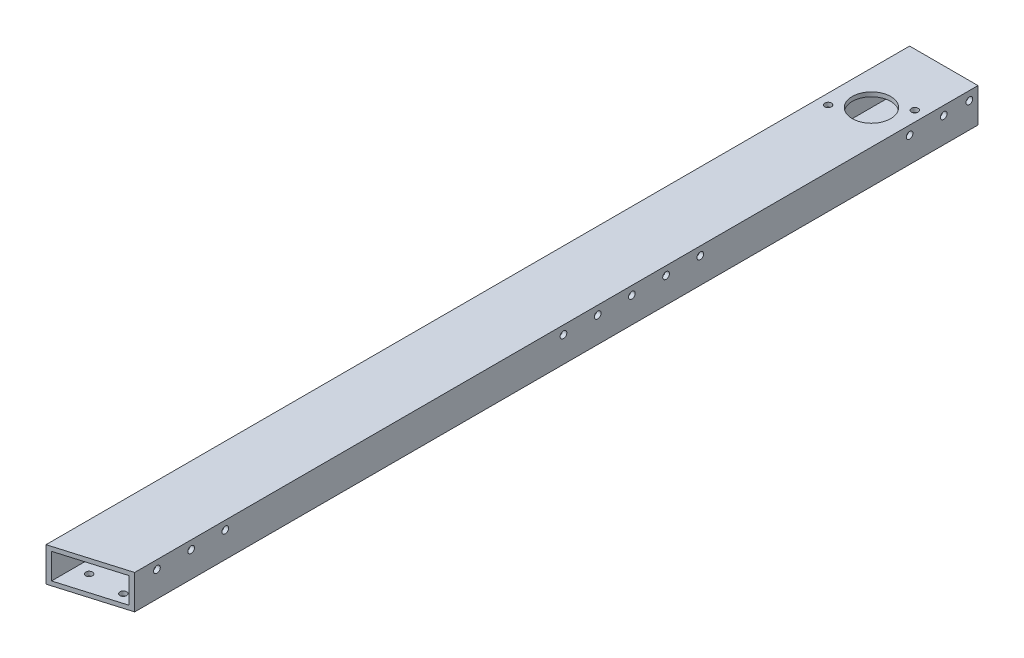
SolidWorks part; units mm, degrees
ref_plane "Front Plane" through (0, 0, 0) normal (0, 0, 1) x (1, 0, 0)
ref_plane "Top Plane" through (0, 0, 0) normal (0, 1, 0) x (1, 0, 0)
ref_plane "Right Plane" through (0, 0, 0) normal (1, 0, 0) x (0, 0, -1)
sketch "Sketch1" plane through (0, 0, 0) normal (0, 0, 1) x (1, 0, 0)
  line L0 (-22.225, 9.525) -> (22.225, 9.525)
  line L2 (-25.4, 12.7) -> (25.4, 12.7)
  line L3 (-25.4, 12.7) -> (-25.4, -12.7)
  line L4 (-25.4, -12.7) -> (25.4, -12.7)
  line L5 (25.4, 12.7) -> (25.4, -12.7)
  line L10 (22.225, 9.525) -> (22.225, -9.525)
  line L11 (-22.225, -9.525) -> (22.225, -9.525)
  line L12 (-22.225, 9.525) -> (-22.225, -9.525)
  point P12 (0, 12.7)
  point P14 (25.4, 0)
  dimension "Wall Thickness" = 3.175
  dimension "Outside Width" = 50.8
  dimension "Outside Height" = 25.4
  dimension "Inside Height" = 19.05
  dimension "Inside Width" = 44.45
sketch "Sketch2" plane through (0, 0, 0) normal (1, 0, 0) x (0, 0, -1)
  line L0 (320.675, 0) -> (-320.675, 0)
  point P4 (0, 0)
  point P7 (-320.675, 0)
  point P10 (320.675, 0)
  dimension "Length" = 641.35
sketch "Sketch3" plane through (0, 0, 0) normal (0, 0, 1) x (1, 0, 0)
  line L21 (25.4, 12.7) -> (-25.4, 12.7)
  line L22 (25.4, -12.7) -> (25.4, 12.7)
  line L23 (-25.4, -12.7) -> (25.4, -12.7)
  line L24 (-25.4, 12.7) -> (-25.4, -12.7)
  line L25 (25.4, 12.7) -> (-25.4, 12.7)
  line L26 (25.4, -12.7) -> (25.4, 12.7)
  line L27 (-25.4, -12.7) -> (25.4, -12.7)
  line L28 (-25.4, 12.7) -> (-25.4, -12.7)
  line L29 (22.225, 9.525) -> (-22.225, 9.525)
  line L30 (22.225, -9.525) -> (22.225, 9.525)
  line L31 (-22.225, -9.525) -> (22.225, -9.525)
  line L32 (-22.225, 9.525) -> (-22.225, -9.525)
  line L33 (22.225, 9.525) -> (-22.225, 9.525)
  line L34 (22.225, -9.525) -> (22.225, 9.525)
  line L35 (-22.225, -9.525) -> (22.225, -9.525)
  line L36 (-22.225, 9.525) -> (-22.225, -9.525)
  dimension "D1" = 0
  dimension "D2" = 0
extrude "Boss-Extrude1" add sketch "Sketch3" along normal up to vertex (320.675 mm away) and the other way up to vertex (320.675 mm away) up to point (0, 0, 320.675) other way up to point (0, 0, -320.675)
sketch "Drawing Reference" plane through (0, 0, 0) normal (1, 0, 0) x (0, 0, -1)
  line L0 (-320.675, 0) -> (320.675, 0) construction
  line L1 (0, -12.7) -> (0, 12.7) construction
  line L2 (-320.675, -12.7) -> (320.675, -12.7) construction
  line L5 (-320.675, 12.7) -> (320.675, 12.7) construction
  point P7 (-284.099, 0)
  point P8 (284.099, 0)
  dimension "D1" = 36.576
sketch "Sketch4" plane through (0, 12.7, 0) normal (0, 1, 0) x (1, 0, 0)
  line L0 (-25.4, -320.675) -> (25.4, -305.6274)
  line L1 (25.4, -320.675) -> (25.4, 320.675) construction
  line L2 (25.4, -320.675) -> (-25.4, -320.675)
  dimension "D1" = 16.5
extrude "Cut-Extrude1" cut sketch "Sketch4" against normal through all and the other way through all flip side to cut
sketch "Sketch8" plane through (0, 12.7, 0) normal (0, 1, 0) x (1, 0, 0)
  line L0 (0, 320.675) -> (0, 266.954) construction
  line L1 (25.4, 320.675) -> (-25.4, 320.675) construction
  circle A0 centre (0, 266.954) radius 14.2875
  dimension "D1" = 53.721
extrude "Cut-Extrude2" cut sketch "Sketch8" against normal through all
sketch "Sketch9" plane through (0, -12.7, 0) normal (0, -1, 0) x (1, 0, 0)
  line L0 (-12.7762, 284.753) -> (-12.7762, 301.263) construction
  line L1 (-12.7762, 301.263) -> (12.6238, 301.263) construction
  line L2 (12.6238, 301.263) -> (12.6238, 284.753) construction
  line L3 (12.6238, 284.753) -> (-12.7762, 284.753) construction
hole_wizard "#10 Clearance Hole1" positions "Sketch10" profile "Sketch11" hole size "#10" standard "ANSI Inch"
sketch "Sketch10" plane through (0, -12.7, 0) normal (0, -1, 0) x (-1, 0, 0)
  point P0 (-12.6238, -284.753)
  point P3 (12.7762, -284.753)
  point P6 (12.7762, -301.263)
  point P9 (-12.6238, -301.263)
sketch "Sketch11" plane through (12.6238, -12.7, 284.753) normal (1, 0, 0) x (0, 0, -1)
  line L0 (0, 0) -> (0, 6.5757)
  line L1 (0, 6.5757) -> (2.4892, 5.08)
  line L2 (2.4892, 5.08) -> (2.4892, 0)
  line L5 (2.4892, 0) -> (0, 0)
  line L10 (0, 6.5757) -> (-2.4892, 5.08) construction
  line L11 (0, -6.35) -> (0, 107.95) construction
  dimension "Hole Dia." = 4.9784
  dimension "Hole Depth" = 5.08
  dimension "Drill Angle" = 118
sketch "Sketch12" plane through (25.4, 0, 0) normal (1, 0, 0) x (0, 0, -1)
  line L0 (320.675, 533.4) -> (-305.6274, 533.4) construction
  line L1 (320.675, 520.7) -> (320.675, 546.1) construction
  line L2 (-305.6274, 546.1) -> (-305.6274, 520.7) construction
hole_wizard "#10 Clearance Hole2" positions "Sketch13" profile "Sketch14" hole size "#10" standard "ANSI Inch"
sketch "Sketch13" plane through (25.4, 0, 0) normal (1, 0, 0) x (0, 0, -1)
  point P0 (314.2868, 6.1483)
  point P3 (295.2368, 6.1483)
  point P6 (269.875, 6.1483)
sketch "Sketch14" plane through (25.4, 6.1483, -314.2868) normal (0, 1, 0) x (0, 0, -1)
  line L0 (0, 0) -> (0, 4.7977)
  line L1 (0, 4.7977) -> (2.4892, 3.302)
  line L2 (2.4892, 3.302) -> (2.4892, 0)
  line L5 (2.4892, 0) -> (0, 0)
  line L10 (0, 4.7977) -> (-2.4892, 3.302) construction
  line L11 (0, -6.35) -> (0, 107.95) construction
  dimension "Hole Dia." = 4.9784
  dimension "Hole Depth" = 3.302
  dimension "Drill Angle" = 118
hole_wizard "#10 Clearance Hole3" positions "Sketch15" profile "Sketch16" hole size "#10" standard "ANSI Inch" end condition through all
sketch "Sketch15" plane through (25.4, 0, 0) normal (1, 0, 0) x (0, 0, -1)
  point P0 (114.427, 6.35)
  point P3 (89.027, 6.35)
  point P6 (63.627, 6.35)
  point P9 (38.227, 6.35)
  point P12 (12.827, 6.35)
  point P24 (-289.0885, 6.3882)
  point P27 (-263.6885, 6.3882)
  point P30 (-238.3267, 6.3882)
sketch "Sketch16" plane through (25.4, 6.35, -114.427) normal (0, 1, 0) x (0, 0, -1)
  line L0 (0, 0) -> (0, 50.8)
  line L1 (0, 50.8) -> (2.4892, 50.8)
  line L2 (2.4892, 50.8) -> (2.4892, 0)
  line L5 (2.4892, 0) -> (0, 0)
  line L11 (0, -6.35) -> (0, 107.95) construction
  dimension "Thru Hole Dia." = 4.9784
  dimension "Thru Hole Depth" = 50.8
sketch "Sketch18" plane through (0, 12.7, 0) normal (0, 1, 0) x (1, 0, 0)
  line L0 (17.786, 281.371) -> (-17.786, 252.537) construction
hole_wizard "#10 Clearance Hole4" positions "Sketch19" profile "Sketch20" hole size "#10" standard "ANSI Inch" end condition through all
sketch "Sketch19" plane through (0, 12.7, 0) normal (0, 1, 0) x (1, 0, 0)
  point P0 (-17.786, 252.537)
  point P3 (17.786, 281.371)
sketch "Sketch20" plane through (-17.786, 12.7, -252.537) normal (1, 0, 0) x (0, 0, 1)
  line L0 (0, 0) -> (0, 25.4)
  line L1 (0, 25.4) -> (5.2197, 25.4)
  line L2 (2.4892, 22.2589) -> (2.4892, 0)
  line L5 (2.4892, 0) -> (0, 0)
  line L7 (5.2197, 25.4) -> (2.4892, 22.2589)
  line L8 (-5.2197, 25.4) -> (-2.4892, 22.2589) construction
  line L11 (0, -6.35) -> (0, 107.95) construction
  dimension "Thru Hole Dia." = 4.9784
  dimension "Thru Hole Depth" = 25.4
  dimension "Far C'Sink Dia." = 10.4394
  dimension "Far C'Sink Angle" = 82
equation "\"D1@Drawing Reference\"=\"Outside Width@Sketch1\" * 0.72"
